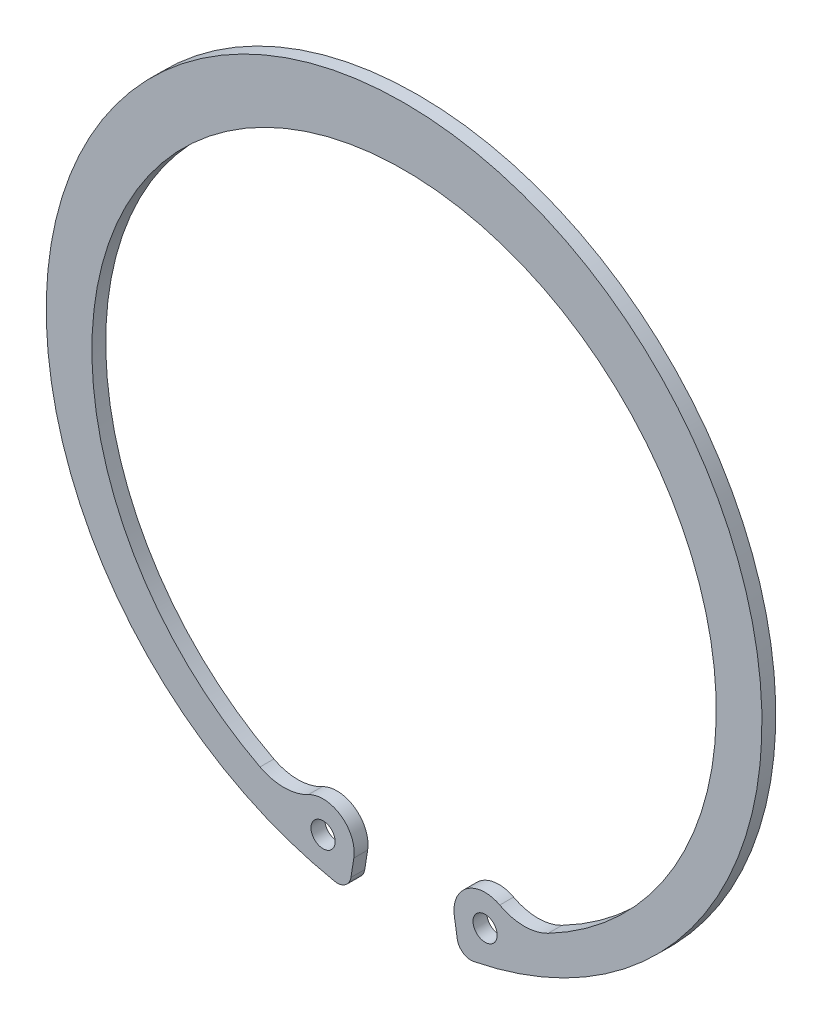
SolidWorks part; units mm, degrees
material "AISI 1020"
ref_plane "Спереди" through (0, 0, 0) normal (0, 0, 1) x (1, 0, 0)
ref_plane "Сверху" through (0, 0, 0) normal (0, 1, 0) x (1, 0, 0)
ref_plane "Справа" through (0, 0, 0) normal (1, 0, 0) x (0, 0, -1)
sketch "Эскиз1" plane through (0, 0, 0) normal (0, 0, 1) x (1, 0, 0)
  line L0 (0, -1000) -> (0, 49000) construction
  line L1 (0, 0) -> (14.5, -46.0197) construction
  line L2 (10.1006, -46.9658) -> (10.6622, -49.577)
  line L3 (0, 44.35) -> (92.3, 44.35) construction
  arc A0 (13.1147, -51.0937) -> (0, 52.75) centre (0, 0) ccw
  circle A2 centre (14.5, -46.0197) radius 1.75
  arc A3 (16.3962, -41.9387) -> (10.1006, -46.9658) centre (14.5, -46.0197) ccw
  arc A4 (16.3962, -41.9387) -> (23.3515, -41.6061) centre (19.5566, -35.1371) ccw
  arc A5 (10.6622, -49.577) -> (13.1147, -51.0937) centre (12.6174, -49.1565) ccw
  arc A6 (23.3515, -41.6061) -> (0, 44.35) centre (0, -1.8) ccw
  dimension "_d2" = 105.5
  dimension "_d4" = 3.5
  dimension "_r1" = 7.5
  dimension "_r2" = 2
  dimension "D1" = 46.15
  dimension "_e" = 1.8
  dimension "_a" = 9
  dimension "_l" = 20
  dimension "_d3" = 92.3
sketch "Эскиз2" plane through (0, 0, 0) normal (0, 0, 1) x (1, 0, 0)
  line L0 (0, -201000) -> (0, 249000) construction
  line L1 (-7.6838, -49.1139) -> (-7.2689, -46.4755)
  line L2 (10.1006, -46.9658) -> (10.6622, -49.577) construction
  line L3 (0, 0) -> (13.1147, -51.0937) construction
  line L4 (0, 0) -> (-10.0479, -50.7652) construction
  line L5 (10.6622, -49.577) -> (13.1147, -51.0937) construction
  line L6 (-10.0479, -50.7652) -> (-7.6838, -49.1139) construction
  line L7 (16.3962, -41.9387) -> (10.1006, -46.9658) construction
  line L8 (-13.8354, -41.8076) -> (-7.2689, -46.4755) construction
  line L9 (0, 51.75) -> (0, 53.75) construction
  circle A0 centre (0, 0) radius 51.75 construction
  circle A1 centre (0, 0) radius 50 construction
  circle A2 centre (0, 0) radius 40.5 construction
  arc A3 (0, 51.75) -> (-10.0479, -50.7652) centre (0, 0) ccw
  arc A4 (0, 43.35) -> (-20.8312, -41.8469) centre (0, -1.7951) ccw
  arc A5 (-10.0479, -50.7652) -> (-7.6838, -49.1139) centre (-9.6596, -48.8032) ccw
  arc A6 (-7.2689, -46.4755) -> (-13.8354, -41.8076) centre (-11.7143, -45.7764) ccw
  arc A7 (10.6622, -49.577) -> (13.1147, -51.0937) centre (12.6174, -49.1565) ccw construction
  arc A8 (16.3962, -41.9387) -> (10.1006, -46.9658) centre (14.5, -46.0197) ccw construction
  arc A9 (-20.8312, -41.8469) -> (-13.8354, -41.8076) centre (-17.3705, -35.193) ccw
  circle A10 centre (-11.7143, -45.7764) radius 1.75
  circle A11 centre (14.5, -46.0197) radius 1.75 construction
  arc A13 (16.3962, -41.9387) -> (23.3515, -41.6061) centre (19.5566, -35.1371) ccw construction
  dimension "_D" = 100
  dimension "_d1" = 103.5
  dimension "_DD" = 81
  dimension "_b" = 8.4
  dimension "D1" = 165.604
  dimension "D2" = 52.75
  dimension "D3" = 168.804
  dimension "_s" = 2
sketch "Эскиз3" plane through (0, 0, 0) normal (0, 0, 1) x (1, 0, 0)
  line L0 (-7.6838, -49.1139) -> (-7.2689, -46.4755) construction
  line L1 (-7.6838, -49.1139) -> (-7.2689, -46.4755)
  line L2 (0, -1000) -> (0, 49000) construction
  line L3 (0, -1000.0733) -> (0, 48999.9267) construction
  line L4 (7.6838, -49.1139) -> (7.2689, -46.4755)
  arc A0 (0, 43.35) -> (-20.8312, -41.8469) centre (0, -1.7951) ccw construction
  arc A1 (-20.8312, -41.8469) -> (-13.8354, -41.8076) centre (-17.3705, -35.193) ccw construction
  arc A2 (-7.2689, -46.4755) -> (-13.8354, -41.8076) centre (-11.7143, -45.7764) ccw construction
  arc A3 (-10.0479, -50.7652) -> (-7.6838, -49.1139) centre (-9.6596, -48.8032) ccw construction
  arc A4 (0, 51.75) -> (-10.0479, -50.7652) centre (0, 0) ccw construction
  arc A5 (20.8312, -41.8469) -> (-20.8312, -41.8469) centre (0, -1.7951) ccw
  arc A6 (-20.8312, -41.8469) -> (-13.8354, -41.8076) centre (-17.3705, -35.193) ccw
  arc A7 (-7.2689, -46.4755) -> (-13.8354, -41.8076) centre (-11.7143, -45.7764) ccw
  arc A8 (-10.0479, -50.7652) -> (-7.6838, -49.1139) centre (-9.6596, -48.8032) ccw
  arc A9 (10.0479, -50.7652) -> (-10.0479, -50.7652) centre (0, 0) ccw
  circle A10 centre (-11.7143, -45.7764) radius 1.75 construction
  circle A11 centre (-11.7143, -45.7764) radius 1.75
  circle A12 centre (11.7143, -45.7764) radius 1.75
  arc A13 (20.8312, -41.8469) -> (13.8354, -41.8076) centre (17.3705, -35.193) cw
  arc A14 (7.2689, -46.4755) -> (13.8354, -41.8076) centre (11.7143, -45.7764) cw
  arc A15 (10.0479, -50.7652) -> (7.6838, -49.1139) centre (9.6596, -48.8032) cw
extrude "Бобышка-Вытянуть1" add sketch "Эскиз3" along normal blind 2
equation "\"D1@Эскиз1\"=\"_d3@Эскиз1\"/2"
equation "\"D3@Эскиз2\"=(\"D2@Эскиз2\"*2*\"D1@Эскиз2\"/360)/(\"_d1@Эскиз2\"/360)"
equation "\"D1@Бобышка-Вытянуть1\"= \"_s@Эскиз2\""
